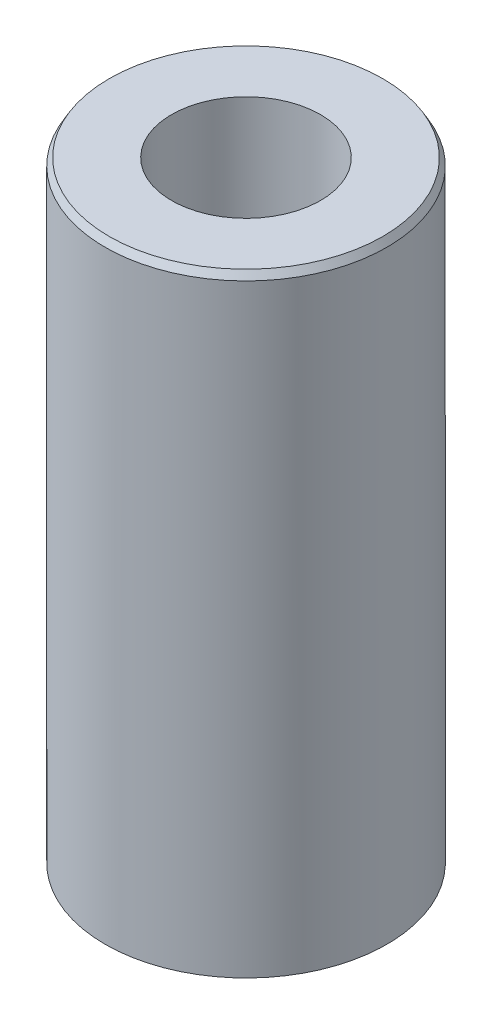
SolidWorks part; units mm, degrees
ref_plane "Front Plane" through (0, 0, 0) normal (0, 0, 1) x (1, 0, 0)
ref_plane "Top Plane" through (0, 0, 0) normal (0, 1, 0) x (1, 0, 0)
ref_plane "Right Plane" through (0, 0, 0) normal (1, 0, 0) x (0, 0, -1)
sketch "Sketch1" plane through (0, 0, 0) normal (0, 1, 0) x (1, 0, 0)
  circle A0 centre (0, 0) radius 27.5
  dimension "SHAFT_OD" = 55
extrude "Boss-Extrude1" add sketch "Sketch1" along normal blind 120.0092
sketch "Sketch2" plane through (0, 0, 0) normal (0, 1, 0) x (1, 0, 0)
  circle A0 centre (0, 0) radius 14.5359
  dimension "BORE_D" = 29.0719
extrude "Cut-Extrude1" cut sketch "Sketch2" along normal through all
chamfer "Chamfer1" distance 1.4123 angle 30 2 edges at (0, 120.0092, 27.5) (0, 0, 27.5) first distance on face at (0, 120.0092, 27.5) first distance on face at (0, 0, 14.5359)
